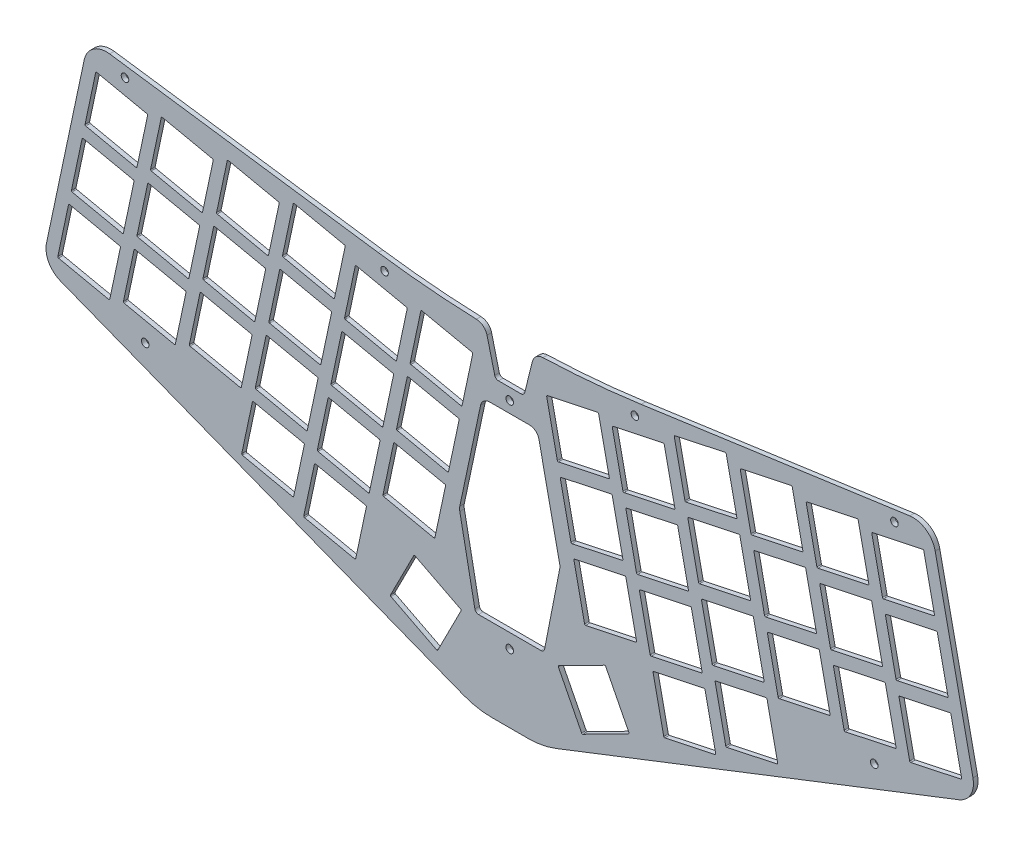
SolidWorks part; units mm, degrees
ref_plane "Front Plane" through (0, 0, 0) normal (0, 0, 1) x (1, 0, 0)
ref_plane "Top Plane" through (0, 0, 0) normal (0, 1, 0) x (1, 0, 0)
ref_plane "Right Plane" through (0, 0, 0) normal (1, 0, 0) x (0, 0, -1)
sketch "Model" plane through (0, 0, 0) normal (0, 0, 1) x (1, 0, 0)
  line L0 (118.9761, -36.3417) -> (119.3386, -36.3417)
  line L1 (109.9761, -36.3417) -> (109.6135, -36.3417)
  line L2 (130.2178, -33.5671) -> (126.6009, -34.9766)
  line L3 (98.7344, -33.5671) -> (102.3512, -34.9766)
  line L4 (114.4761, -36.3417) -> (109.9761, -36.3417)
  line L5 (114.4761, -36.3417) -> (118.9761, -36.3417)
  line L6 (118.4251, 42.1791) -> (120.4508, 50.3035)
  line L7 (110.527, 42.1791) -> (108.5014, 50.3035)
  line L8 (130.2178, -33.5671) -> (232.9153, 6.4558)
  line L9 (236.6055, 13.2938) -> (226.6558, 60.1035)
  line L10 (219.9519, 64.7976) -> (149.1302, 54.8443)
  line L11 (79.822, 54.8443) -> (9.0003, 64.7976)
  line L12 (2.2964, 60.1035) -> (-7.6533, 13.2938)
  line L13 (-3.9631, 6.4558) -> (98.7344, -33.5671)
  line L14 (111.4973, 41.421) -> (117.4548, 41.421)
  line L15 (119.9761, -34.3417) -> (108.9761, -34.3417)
  line L16 (120.4761, -22.3417) -> (120.4761, -33.8417)
  line L17 (108.9761, -21.8417) -> (119.9761, -21.8417)
  line L18 (108.4761, -33.8417) -> (108.4761, -22.3417)
  line L19 (123.6714, -13.7578) -> (127.6435, 6.5155)
  line L20 (105.2808, -13.7578) -> (101.3087, 6.5155)
  line L21 (106.2621, -14.5655) -> (122.69, -14.5655)
  line L22 (109.4761, 35.421) -> (109.2316, 35.421)
  line L23 (119.4761, 35.421) -> (119.7205, 35.421)
  line L24 (109.4761, 35.421) -> (119.4761, 35.421)
  line L25 (127.6339, 7.716) -> (122.1659, 33.4408)
  line L26 (101.3183, 7.716) -> (106.7863, 33.4408)
  line L27 (230.5128, 25.1235) -> (217.3078, 22.3167)
  line L28 (217.1153, 22.0202) -> (219.9221, 8.8152)
  line L29 (220.2186, 8.6226) -> (233.4236, 11.4294)
  line L30 (233.6161, 11.7259) -> (230.8093, 24.9309)
  line L31 (226.9263, 41.9965) -> (213.7213, 39.1897)
  line L32 (213.5288, 38.8932) -> (216.3356, 25.6882)
  line L33 (216.6321, 25.4957) -> (229.8371, 28.3025)
  line L34 (230.0297, 28.599) -> (227.2228, 41.804)
  line L35 (223.3399, 58.8696) -> (210.1349, 56.0628)
  line L36 (209.9423, 55.7663) -> (212.7491, 42.5613)
  line L37 (213.0456, 42.3687) -> (226.2506, 45.1755)
  line L38 (226.4432, 45.472) -> (223.6364, 58.677)
  line L39 (213.2239, 23.4933) -> (200.0189, 20.6865)
  line L40 (199.8264, 20.39) -> (202.6332, 7.185)
  line L41 (202.9297, 6.9924) -> (216.1347, 9.7992)
  line L42 (216.3273, 10.0958) -> (213.5205, 23.3007)
  line L43 (209.6375, 40.3663) -> (196.4325, 37.5595)
  line L44 (196.2399, 37.263) -> (199.0467, 24.058)
  line L45 (199.3432, 23.8655) -> (212.5482, 26.6723)
  line L46 (212.7408, 26.9688) -> (209.934, 40.1738)
  line L47 (206.051, 57.2394) -> (192.846, 54.4326)
  line L48 (192.6534, 54.1361) -> (195.4602, 40.9311)
  line L49 (195.7568, 40.7385) -> (208.9618, 43.5453)
  line L50 (209.1543, 43.8418) -> (206.3475, 57.0468)
  line L51 (195.8311, 22.3522) -> (182.6261, 19.5454)
  line L52 (182.4336, 19.2489) -> (185.2404, 6.0439)
  line L53 (185.5369, 5.8513) -> (198.7419, 8.6581)
  line L54 (198.9344, 8.9546) -> (196.1276, 22.1596)
  line L55 (192.2446, 39.2252) -> (179.0396, 36.4184)
  line L56 (178.8471, 36.1219) -> (181.6539, 22.9169)
  line L57 (181.9504, 22.7244) -> (195.1554, 25.5312)
  line L58 (195.348, 25.8277) -> (192.5412, 39.0327)
  line L59 (188.6582, 56.0983) -> (175.4532, 53.2915)
  line L60 (175.2606, 52.995) -> (178.0674, 39.79)
  line L61 (178.3639, 39.5974) -> (191.5689, 42.4042)
  line L62 (191.7615, 42.7007) -> (188.9547, 55.9057)
  line L63 (182.0248, 4.338) -> (168.8198, 1.5312)
  line L64 (168.6272, 1.2347) -> (171.434, -11.9703)
  line L65 (171.7305, -12.1628) -> (184.9355, -9.356)
  line L66 (185.1281, -9.0595) -> (182.3213, 4.1455)
  line L67 (178.4383, 21.2111) -> (165.2333, 18.4043)
  line L68 (165.0407, 18.1078) -> (167.8475, 4.9028)
  line L69 (168.1441, 4.7102) -> (181.3491, 7.517)
  line L70 (181.5416, 7.8135) -> (178.7348, 21.0185)
  line L71 (174.8518, 38.0841) -> (161.6468, 35.2773)
  line L72 (161.4543, 34.9808) -> (164.2611, 21.7758)
  line L73 (164.5576, 21.5833) -> (177.7626, 24.3901)
  line L74 (177.9551, 24.6866) -> (175.1483, 37.8916)
  line L75 (171.2653, 54.9572) -> (158.0603, 52.1504)
  line L76 (157.8678, 51.8539) -> (160.6746, 38.6489)
  line L77 (160.9711, 38.4563) -> (174.1761, 41.2631)
  line L78 (174.3687, 41.5596) -> (171.5619, 54.7646)
  line L79 (165.6715, -1.6938) -> (152.4665, -4.5006)
  line L80 (152.2739, -4.7971) -> (155.0808, -18.0021)
  line L81 (155.3773, -18.1947) -> (168.5823, -15.3879)
  line L82 (168.7748, -15.0914) -> (165.968, -1.8864)
  line L83 (162.085, 15.1792) -> (148.88, 12.3724)
  line L84 (148.6875, 12.0759) -> (151.4943, -1.1291)
  line L85 (151.7908, -1.3216) -> (164.9958, 1.4852)
  line L86 (165.1883, 1.7817) -> (162.3815, 14.9867)
  line L87 (158.4985, 32.0523) -> (145.2936, 29.2455)
  line L88 (145.101, 28.949) -> (147.9078, 15.744)
  line L89 (148.2043, 15.5514) -> (161.4093, 18.3582)
  line L90 (161.6019, 18.6547) -> (158.7951, 31.8597)
  line L91 (154.9121, 48.9253) -> (141.7071, 46.1185)
  line L92 (141.5145, 45.822) -> (144.3213, 32.617)
  line L93 (144.6178, 32.4245) -> (157.8228, 35.2313)
  line L94 (158.0154, 35.5278) -> (155.2086, 48.7328)
  line L95 (137.6232, 47.2952) -> (124.4182, 44.4883)
  line L96 (124.2256, 44.1918) -> (127.0325, 30.9868)
  line L97 (127.329, 30.7943) -> (140.534, 33.6011)
  line L98 (140.7265, 33.8976) -> (137.9197, 47.1026)
  line L99 (141.2097, 30.4221) -> (128.0047, 27.6153)
  line L100 (127.8121, 27.3188) -> (130.6189, 14.1138)
  line L101 (130.9154, 13.9212) -> (144.1204, 16.728)
  line L102 (144.313, 17.0246) -> (141.5062, 30.2295)
  line L103 (144.7962, 13.5491) -> (131.5912, 10.7423)
  line L104 (131.3986, 10.4457) -> (134.2054, -2.7593)
  line L105 (134.5019, -2.9518) -> (147.7069, -0.145)
  line L106 (147.8995, 0.1515) -> (145.0927, 13.3565)
  line L107 (139.4422, -9.5606) -> (127.4136, -15.6895)
  line L108 (127.3043, -16.0257) -> (133.4332, -28.0543)
  line L109 (133.7695, -28.1635) -> (145.7981, -22.0347)
  line L110 (145.9073, -21.6984) -> (139.7784, -9.6698)
  line L111 (101.5386, -15.6895) -> (89.51, -9.5606)
  line L112 (89.1737, -9.6698) -> (83.0449, -21.6984)
  line L113 (83.1541, -22.0347) -> (95.1827, -28.1635)
  line L114 (95.519, -28.0543) -> (101.6478, -16.0257)
  line L115 (97.361, 10.7423) -> (84.156, 13.5491)
  line L116 (83.8595, 13.3565) -> (81.0527, 0.1515)
  line L117 (81.2453, -0.145) -> (94.4502, -2.9518)
  line L118 (94.7468, -2.7593) -> (97.5536, 10.4457)
  line L119 (100.9475, 27.6153) -> (87.7425, 30.4221)
  line L120 (87.446, 30.2295) -> (84.6392, 17.0246)
  line L121 (84.8317, 16.728) -> (98.0367, 13.9212)
  line L122 (98.3332, 14.1138) -> (101.14, 27.3188)
  line L123 (104.534, 44.4883) -> (91.329, 47.2952)
  line L124 (91.0325, 47.1026) -> (88.2256, 33.8976)
  line L125 (88.4182, 33.6011) -> (101.6232, 30.7943)
  line L126 (101.9197, 30.9868) -> (104.7265, 44.1918)
  line L127 (76.4857, -4.5006) -> (63.2807, -1.6938)
  line L128 (62.9842, -1.8864) -> (60.1773, -15.0914)
  line L129 (60.3699, -15.3879) -> (73.5749, -18.1947)
  line L130 (73.8714, -18.0021) -> (76.6782, -4.7971)
  line L131 (80.0721, 12.3724) -> (66.8671, 15.1792)
  line L132 (66.5706, 14.9867) -> (63.7638, 1.7817)
  line L133 (63.9564, 1.4852) -> (77.1614, -1.3216)
  line L134 (77.4579, -1.1291) -> (80.2647, 12.0759)
  line L135 (83.6586, 29.2455) -> (70.4536, 32.0523)
  line L136 (70.1571, 31.8597) -> (67.3503, 18.6547)
  line L137 (67.5429, 18.3582) -> (80.7479, 15.5514)
  line L138 (81.0444, 15.744) -> (83.8512, 28.949)
  line L139 (87.2451, 46.1185) -> (74.0401, 48.9253)
  line L140 (73.7436, 48.7328) -> (70.9368, 35.5278)
  line L141 (71.1293, 35.2313) -> (84.3343, 32.4245)
  line L142 (84.6308, 32.617) -> (87.4377, 45.822)
  line L143 (60.1324, 1.5312) -> (46.9274, 4.338)
  line L144 (46.6309, 4.1455) -> (43.8241, -9.0595)
  line L145 (44.0166, -9.356) -> (57.2216, -12.1628)
  line L146 (57.5181, -11.9703) -> (60.325, 1.2347)
  line L147 (63.7189, 18.4043) -> (50.5139, 21.2111)
  line L148 (50.2174, 21.0185) -> (47.4106, 7.8135)
  line L149 (47.6031, 7.517) -> (60.8081, 4.7102)
  line L150 (61.1046, 4.9028) -> (63.9114, 18.1078)
  line L151 (67.3054, 35.2773) -> (54.1004, 38.0841)
  line L152 (53.8038, 37.8916) -> (50.997, 24.6866)
  line L153 (51.1896, 24.3901) -> (64.3946, 21.5833)
  line L154 (64.6911, 21.7758) -> (67.4979, 34.9808)
  line L155 (70.8918, 52.1504) -> (57.6868, 54.9572)
  line L156 (57.3903, 54.7646) -> (54.5835, 41.5596)
  line L157 (54.7761, 41.2631) -> (67.9811, 38.4563)
  line L158 (68.2776, 38.6489) -> (71.0844, 51.8539)
  line L159 (46.5186, 19.2489) -> (45.1152, 12.6464)
  line L160 (33.1211, 22.3522) -> (46.326, 19.5454)
  line L161 (30.0177, 8.9546) -> (32.8245, 22.1596)
  line L162 (43.4153, 5.8513) -> (30.2103, 8.6581)
  line L163 (45.1152, 12.6464) -> (43.7118, 6.0439)
  line L164 (50.1051, 36.1219) -> (48.7017, 29.5194)
  line L165 (36.7075, 39.2252) -> (49.9125, 36.4184)
  line L166 (33.6042, 25.8277) -> (36.411, 39.0327)
  line L167 (47.0018, 22.7244) -> (33.7968, 25.5312)
  line L168 (48.7017, 29.5194) -> (47.2983, 22.9169)
  line L169 (53.6916, 52.995) -> (52.2882, 46.3925)
  line L170 (40.294, 56.0983) -> (53.499, 53.2915)
  line L171 (37.1907, 42.7007) -> (39.9975, 55.9057)
  line L172 (50.5882, 39.5974) -> (37.3832, 42.4042)
  line L173 (52.2882, 46.3925) -> (50.8848, 39.79)
  line L174 (29.1258, 20.39) -> (27.7224, 13.7875)
  line L175 (15.7282, 23.4933) -> (28.9332, 20.6865)
  line L176 (12.6249, 10.0958) -> (15.4317, 23.3007)
  line L177 (26.0225, 6.9924) -> (12.8175, 9.7992)
  line L178 (27.7224, 13.7875) -> (26.319, 7.185)
  line L179 (32.7123, 37.263) -> (31.3089, 30.6605)
  line L180 (19.3147, 40.3663) -> (32.5197, 37.5595)
  line L181 (16.2114, 26.9688) -> (19.0182, 40.1738)
  line L182 (29.6089, 23.8655) -> (16.4039, 26.6723)
  line L183 (31.3089, 30.6605) -> (29.9055, 24.058)
  line L184 (19.7979, 43.8418) -> (21.2013, 50.4443)
  line L185 (33.1954, 40.7385) -> (19.9904, 43.5453)
  line L186 (36.2987, 54.1361) -> (33.4919, 40.9311)
  line L187 (22.9012, 57.2394) -> (36.1062, 54.4326)
  line L188 (21.2013, 50.4443) -> (22.6047, 57.0468)
  line L189 (-4.664, 11.7259) -> (-3.2606, 18.3284)
  line L190 (8.7336, 8.6226) -> (-4.4714, 11.4294)
  line L191 (11.8369, 22.0202) -> (9.0301, 8.8152)
  line L192 (-1.5606, 25.1235) -> (11.6444, 22.3167)
  line L193 (-3.2606, 18.3284) -> (-1.8572, 24.9309)
  line L194 (15.2308, 39.1897) -> (8.6283, 40.5931)
  line L195 (12.6166, 25.6882) -> (15.4234, 38.8932)
  line L196 (-0.8849, 28.3025) -> (12.3201, 25.4957)
  line L197 (1.7293, 41.804) -> (-1.0775, 28.599)
  line L198 (8.6283, 40.5931) -> (2.0258, 41.9965)
  line L199 (2.509, 45.472) -> (3.9124, 52.0745)
  line L200 (15.9065, 42.3687) -> (2.7016, 45.1755)
  line L201 (19.0099, 55.7663) -> (16.2031, 42.5613)
  line L202 (5.6123, 58.8696) -> (18.8173, 56.0628)
  line L203 (3.9124, 52.0745) -> (5.3158, 58.677)
  line L206 (114.4761, -19.3417) -> (114.4761, -17.3417) construction
  line L207 (115.4761, -18.3417) -> (113.4761, -18.3417) construction
  circle A0 centre (215.9057, 61.3788) radius 1
  circle A1 centre (13.0465, 61.3788) radius 1
  circle A2 centre (148.1114, -4.3098) radius 1
  circle A3 centre (80.8407, -4.3098) radius 1
  circle A4 centre (210.5718, 3.5051) radius 1
  circle A5 centre (147.4779, 51.4345) radius 1
  circle A6 centre (81.4742, 51.4345) radius 1
  circle A7 centre (18.3804, 3.5051) radius 1
  circle A8 centre (114.4761, -18.3417) radius 1
  circle A9 centre (114.4761, 38.421) radius 1
  arc A10 (108.4761, -33.8417) -> (108.9761, -34.3417) centre (108.9761, -33.8417) ccw
  arc A11 (119.9761, -34.3417) -> (120.4761, -33.8417) centre (119.9761, -33.8417) ccw
  arc A12 (120.4761, -22.3417) -> (119.9761, -21.8417) centre (119.9761, -22.3417) ccw
  arc A13 (108.9761, -21.8417) -> (108.4761, -22.3417) centre (108.9761, -22.3417) ccw
  arc A14 (122.69, -14.5655) -> (123.6714, -13.7578) centre (122.69, -13.5655) ccw
  arc A15 (105.2808, -13.7578) -> (106.2621, -14.5655) centre (106.2621, -13.5655) ccw
  arc A16 (127.6435, 6.5155) -> (127.6339, 7.716) centre (124.6994, 7.0923) ccw
  arc A17 (101.3183, 7.716) -> (101.3087, 6.5155) centre (104.2527, 7.0923) ccw
  arc A18 (122.1659, 33.4408) -> (119.7205, 35.421) centre (119.7205, 32.921) ccw
  arc A19 (109.2316, 35.421) -> (106.7863, 33.4408) centre (109.2316, 32.921) ccw
  arc A20 (46.5186, 19.2489) -> (46.326, 19.5454) centre (46.2741, 19.3008) ccw
  arc A21 (30.0177, 8.9546) -> (30.2103, 8.6581) centre (30.2623, 8.9027) ccw
  arc A22 (33.1211, 22.3522) -> (32.8245, 22.1596) centre (33.0691, 22.1077) ccw
  arc A23 (43.4153, 5.8513) -> (43.7118, 6.0439) centre (43.4673, 6.0959) ccw
  arc A24 (50.1051, 36.1219) -> (49.9125, 36.4184) centre (49.8605, 36.1739) ccw
  arc A25 (36.7075, 39.2252) -> (36.411, 39.0327) centre (36.6556, 38.9807) ccw
  arc A26 (33.6042, 25.8277) -> (33.7968, 25.5312) centre (33.8487, 25.7757) ccw
  arc A27 (47.0018, 22.7244) -> (47.2983, 22.9169) centre (47.0537, 22.9689) ccw
  arc A28 (53.6916, 52.995) -> (53.499, 53.2915) centre (53.447, 53.0469) ccw
  arc A29 (40.294, 56.0983) -> (39.9975, 55.9057) centre (40.242, 55.8537) ccw
  arc A30 (37.1907, 42.7007) -> (37.3832, 42.4042) centre (37.4352, 42.6488) ccw
  arc A31 (50.5882, 39.5974) -> (50.8848, 39.79) centre (50.6402, 39.8419) ccw
  arc A32 (29.1258, 20.39) -> (28.9332, 20.6865) centre (28.8812, 20.442) ccw
  arc A33 (15.7282, 23.4933) -> (15.4317, 23.3007) centre (15.6763, 23.2488) ccw
  arc A34 (12.6249, 10.0958) -> (12.8175, 9.7992) centre (12.8694, 10.0438) ccw
  arc A35 (26.0225, 6.9924) -> (26.319, 7.185) centre (26.0744, 7.237) ccw
  arc A36 (19.3147, 40.3663) -> (19.0182, 40.1738) centre (19.2627, 40.1218) ccw
  arc A37 (32.7123, 37.263) -> (32.5197, 37.5595) centre (32.4677, 37.315) ccw
  arc A38 (16.2114, 26.9688) -> (16.4039, 26.6723) centre (16.4559, 26.9168) ccw
  arc A39 (29.6089, 23.8655) -> (29.9055, 24.058) centre (29.6609, 24.11) ccw
  arc A40 (19.7979, 43.8418) -> (19.9904, 43.5453) centre (20.0424, 43.7899) ccw
  arc A41 (36.2987, 54.1361) -> (36.1062, 54.4326) centre (36.0542, 54.188) ccw
  arc A42 (33.1954, 40.7385) -> (33.4919, 40.9311) centre (33.2474, 40.9831) ccw
  arc A43 (22.9012, 57.2394) -> (22.6047, 57.0468) centre (22.8492, 56.9949) ccw
  arc A44 (-4.664, 11.7259) -> (-4.4714, 11.4294) centre (-4.4194, 11.674) ccw
  arc A45 (11.8369, 22.0202) -> (11.6444, 22.3167) centre (11.5924, 22.0721) ccw
  arc A46 (8.7336, 8.6226) -> (9.0301, 8.8152) centre (8.7856, 8.8671) ccw
  arc A47 (-1.5606, 25.1235) -> (-1.8572, 24.9309) centre (-1.6126, 24.8789) ccw
  arc A48 (15.4234, 38.8932) -> (15.2308, 39.1897) centre (15.1789, 38.9452) ccw
  arc A49 (12.3201, 25.4957) -> (12.6166, 25.6882) centre (12.372, 25.7402) ccw
  arc A50 (-1.0775, 28.599) -> (-0.8849, 28.3025) centre (-0.8329, 28.547) ccw
  arc A51 (2.0258, 41.9965) -> (1.7293, 41.804) centre (1.9739, 41.752) ccw
  arc A52 (2.509, 45.472) -> (2.7016, 45.1755) centre (2.7535, 45.42) ccw
  arc A53 (19.0099, 55.7663) -> (18.8173, 56.0628) centre (18.7653, 55.8182) ccw
  arc A54 (15.9065, 42.3687) -> (16.2031, 42.5613) centre (15.9585, 42.6132) ccw
  arc A55 (5.6123, 58.8696) -> (5.3158, 58.677) centre (5.5603, 58.625) ccw
  arc A56 (102.3512, -34.9766) -> (109.6135, -36.3417) centre (109.6135, -16.3417) ccw
  arc A57 (119.3386, -36.3417) -> (126.6009, -34.9766) centre (119.3386, -16.3417) ccw
  arc A58 (108.5014, 50.3035) -> (105.6963, 52.5758) centre (105.5905, 49.5777) ccw
  arc A59 (123.2559, 52.5758) -> (120.4508, 50.3035) centre (123.3617, 49.5777) ccw
  arc A60 (117.4548, 41.421) -> (118.4251, 42.1791) centre (117.4548, 42.421) ccw
  arc A61 (110.527, 42.1791) -> (111.4973, 41.421) centre (111.4973, 42.421) ccw
  arc A62 (232.9153, 6.4558) -> (236.6055, 13.2938) centre (230.7366, 12.0463) ccw
  arc A63 (226.6558, 60.1035) -> (219.9519, 64.7976) centre (220.7869, 58.856) ccw
  arc A64 (123.2559, 52.5758) -> (149.1302, 54.8443) centre (114.4761, 301.421) ccw
  arc A65 (79.822, 54.8443) -> (105.6963, 52.5758) centre (114.4761, 301.421) ccw
  arc A66 (9.0003, 64.7976) -> (2.2964, 60.1035) centre (8.1653, 58.856) ccw
  arc A67 (-7.6533, 13.2938) -> (-3.9631, 6.4558) centre (-1.7844, 12.0463) ccw
  arc A68 (217.3078, 22.3167) -> (217.1153, 22.0202) centre (217.3598, 22.0721) ccw
  arc A69 (219.9221, 8.8152) -> (220.2186, 8.6226) centre (220.1666, 8.8671) ccw
  arc A70 (233.4236, 11.4294) -> (233.6161, 11.7259) centre (233.3716, 11.674) ccw
  arc A71 (230.8093, 24.9309) -> (230.5128, 25.1235) centre (230.5648, 24.8789) ccw
  arc A72 (213.7213, 39.1897) -> (213.5288, 38.8932) centre (213.7733, 38.9452) ccw
  arc A73 (216.3356, 25.6882) -> (216.6321, 25.4957) centre (216.5801, 25.7402) ccw
  arc A74 (229.8371, 28.3025) -> (230.0297, 28.599) centre (229.7851, 28.547) ccw
  arc A75 (227.2228, 41.804) -> (226.9263, 41.9965) centre (226.9783, 41.752) ccw
  arc A76 (210.1349, 56.0628) -> (209.9423, 55.7663) centre (210.1868, 55.8182) ccw
  arc A77 (212.7491, 42.5613) -> (213.0456, 42.3687) centre (212.9937, 42.6132) ccw
  arc A78 (226.2506, 45.1755) -> (226.4432, 45.472) centre (226.1986, 45.42) ccw
  arc A79 (223.6364, 58.677) -> (223.3399, 58.8696) centre (223.3918, 58.625) ccw
  arc A80 (200.0189, 20.6865) -> (199.8264, 20.39) centre (200.0709, 20.442) ccw
  arc A81 (202.6332, 7.185) -> (202.9297, 6.9924) centre (202.8777, 7.237) ccw
  arc A82 (216.1347, 9.7992) -> (216.3273, 10.0958) centre (216.0827, 10.0438) ccw
  arc A83 (213.5205, 23.3007) -> (213.2239, 23.4933) centre (213.2759, 23.2488) ccw
  arc A84 (196.4325, 37.5595) -> (196.2399, 37.263) centre (196.4845, 37.315) ccw
  arc A85 (199.0467, 24.058) -> (199.3432, 23.8655) centre (199.2913, 24.11) ccw
  arc A86 (212.5482, 26.6723) -> (212.7408, 26.9688) centre (212.4963, 26.9168) ccw
  arc A87 (209.934, 40.1738) -> (209.6375, 40.3663) centre (209.6894, 40.1218) ccw
  arc A88 (192.846, 54.4326) -> (192.6534, 54.1361) centre (192.898, 54.188) ccw
  arc A89 (195.4602, 40.9311) -> (195.7568, 40.7385) centre (195.7048, 40.9831) ccw
  arc A90 (208.9618, 43.5453) -> (209.1543, 43.8418) centre (208.9098, 43.7899) ccw
  arc A91 (206.3475, 57.0468) -> (206.051, 57.2394) centre (206.103, 56.9949) ccw
  arc A92 (182.6261, 19.5454) -> (182.4336, 19.2489) centre (182.6781, 19.3008) ccw
  arc A93 (185.2404, 6.0439) -> (185.5369, 5.8513) centre (185.4849, 6.0959) ccw
  arc A94 (198.7419, 8.6581) -> (198.9344, 8.9546) centre (198.6899, 8.9027) ccw
  arc A95 (196.1276, 22.1596) -> (195.8311, 22.3522) centre (195.8831, 22.1077) ccw
  arc A96 (179.0396, 36.4184) -> (178.8471, 36.1219) centre (179.0916, 36.1739) ccw
  arc A97 (181.6539, 22.9169) -> (181.9504, 22.7244) centre (181.8984, 22.9689) ccw
  arc A98 (195.1554, 25.5312) -> (195.348, 25.8277) centre (195.1034, 25.7757) ccw
  arc A99 (192.5412, 39.0327) -> (192.2446, 39.2252) centre (192.2966, 38.9807) ccw
  arc A100 (175.4532, 53.2915) -> (175.2606, 52.995) centre (175.5051, 53.0469) ccw
  arc A101 (178.0674, 39.79) -> (178.3639, 39.5974) centre (178.312, 39.8419) ccw
  arc A102 (191.5689, 42.4042) -> (191.7615, 42.7007) centre (191.5169, 42.6488) ccw
  arc A103 (188.9547, 55.9057) -> (188.6582, 56.0983) centre (188.7101, 55.8537) ccw
  arc A104 (168.8198, 1.5312) -> (168.6272, 1.2347) centre (168.8718, 1.2867) ccw
  arc A105 (171.434, -11.9703) -> (171.7305, -12.1628) centre (171.6786, -11.9183) ccw
  arc A106 (184.9355, -9.356) -> (185.1281, -9.0595) centre (184.8836, -9.1115) ccw
  arc A107 (182.3213, 4.1455) -> (182.0248, 4.338) centre (182.0767, 4.0935) ccw
  arc A108 (165.2333, 18.4043) -> (165.0407, 18.1078) centre (165.2853, 18.1597) ccw
  arc A109 (167.8475, 4.9028) -> (168.1441, 4.7102) centre (168.0921, 4.9547) ccw
  arc A110 (181.3491, 7.517) -> (181.5416, 7.8135) centre (181.2971, 7.7616) ccw
  arc A111 (178.7348, 21.0185) -> (178.4383, 21.2111) centre (178.4903, 20.9665) ccw
  arc A112 (161.6468, 35.2773) -> (161.4543, 34.9808) centre (161.6988, 35.0328) ccw
  arc A113 (164.2611, 21.7758) -> (164.5576, 21.5833) centre (164.5056, 21.8278) ccw
  arc A114 (177.7626, 24.3901) -> (177.9551, 24.6866) centre (177.7106, 24.6346) ccw
  arc A115 (175.1483, 37.8916) -> (174.8518, 38.0841) centre (174.9038, 37.8396) ccw
  arc A116 (158.0603, 52.1504) -> (157.8678, 51.8539) centre (158.1123, 51.9058) ccw
  arc A117 (160.6746, 38.6489) -> (160.9711, 38.4563) centre (160.9191, 38.7008) ccw
  arc A118 (174.1761, 41.2631) -> (174.3687, 41.5596) centre (174.1241, 41.5076) ccw
  arc A119 (171.5619, 54.7646) -> (171.2653, 54.9572) centre (171.3173, 54.7126) ccw
  arc A120 (152.4665, -4.5006) -> (152.2739, -4.7971) centre (152.5185, -4.7452) ccw
  arc A121 (155.0808, -18.0021) -> (155.3773, -18.1947) centre (155.3253, -17.9501) ccw
  arc A122 (168.5823, -15.3879) -> (168.7748, -15.0914) centre (168.5303, -15.1433) ccw
  arc A123 (165.968, -1.8864) -> (165.6715, -1.6938) centre (165.7235, -1.9383) ccw
  arc A124 (148.88, 12.3724) -> (148.6875, 12.0759) centre (148.932, 12.1279) ccw
  arc A125 (151.4943, -1.1291) -> (151.7908, -1.3216) centre (151.7388, -1.0771) ccw
  arc A126 (164.9958, 1.4852) -> (165.1883, 1.7817) centre (164.9438, 1.7297) ccw
  arc A127 (162.3815, 14.9867) -> (162.085, 15.1792) centre (162.137, 14.9347) ccw
  arc A128 (145.2936, 29.2455) -> (145.101, 28.949) centre (145.3455, 29.0009) ccw
  arc A129 (147.9078, 15.744) -> (148.2043, 15.5514) centre (148.1523, 15.7959) ccw
  arc A130 (161.4093, 18.3582) -> (161.6019, 18.6547) centre (161.3573, 18.6028) ccw
  arc A131 (158.7951, 31.8597) -> (158.4985, 32.0523) centre (158.5505, 31.8078) ccw
  arc A132 (141.7071, 46.1185) -> (141.5145, 45.822) centre (141.7591, 45.874) ccw
  arc A133 (144.3213, 32.617) -> (144.6178, 32.4245) centre (144.5659, 32.669) ccw
  arc A134 (157.8228, 35.2313) -> (158.0154, 35.5278) centre (157.7709, 35.4758) ccw
  arc A135 (155.2086, 48.7328) -> (154.9121, 48.9253) centre (154.964, 48.6808) ccw
  arc A136 (124.4182, 44.4883) -> (124.2256, 44.1918) centre (124.4702, 44.2438) ccw
  arc A137 (127.0325, 30.9868) -> (127.329, 30.7943) centre (127.277, 31.0388) ccw
  arc A138 (140.534, 33.6011) -> (140.7265, 33.8976) centre (140.482, 33.8456) ccw
  arc A139 (137.9197, 47.1026) -> (137.6232, 47.2952) centre (137.6752, 47.0506) ccw
  arc A140 (128.0047, 27.6153) -> (127.8121, 27.3188) centre (128.0567, 27.3708) ccw
  arc A141 (130.6189, 14.1138) -> (130.9154, 13.9212) centre (130.8635, 14.1658) ccw
  arc A142 (144.1204, 16.728) -> (144.313, 17.0246) centre (144.0685, 16.9726) ccw
  arc A143 (141.5062, 30.2295) -> (141.2097, 30.4221) centre (141.2617, 30.1776) ccw
  arc A144 (131.5912, 10.7423) -> (131.3986, 10.4457) centre (131.6431, 10.4977) ccw
  arc A145 (134.2054, -2.7593) -> (134.5019, -2.9518) centre (134.4499, -2.7073) ccw
  arc A146 (147.7069, -0.145) -> (147.8995, 0.1515) centre (147.6549, 0.0995) ccw
  arc A147 (145.0927, 13.3565) -> (144.7962, 13.5491) centre (144.8481, 13.3045) ccw
  arc A148 (127.4136, -15.6895) -> (127.3043, -16.0257) centre (127.5271, -15.9122) ccw
  arc A149 (133.4332, -28.0543) -> (133.7695, -28.1635) centre (133.656, -27.9408) ccw
  arc A150 (145.7981, -22.0347) -> (145.9073, -21.6984) centre (145.6846, -21.8119) ccw
  arc A151 (139.7784, -9.6698) -> (139.4422, -9.5606) centre (139.5557, -9.7833) ccw
  arc A152 (89.51, -9.5606) -> (89.1737, -9.6698) centre (89.3965, -9.7833) ccw
  arc A153 (83.0449, -21.6984) -> (83.1541, -22.0347) centre (83.2676, -21.8119) ccw
  arc A154 (95.1827, -28.1635) -> (95.519, -28.0543) centre (95.2962, -27.9408) ccw
  arc A155 (101.6478, -16.0257) -> (101.5386, -15.6895) centre (101.4251, -15.9122) ccw
  arc A156 (84.156, 13.5491) -> (83.8595, 13.3565) centre (84.104, 13.3045) ccw
  arc A157 (81.0527, 0.1515) -> (81.2453, -0.145) centre (81.2972, 0.0995) ccw
  arc A158 (94.4502, -2.9518) -> (94.7468, -2.7593) centre (94.5022, -2.7073) ccw
  arc A159 (97.5536, 10.4457) -> (97.361, 10.7423) centre (97.309, 10.4977) ccw
  arc A160 (87.7425, 30.4221) -> (87.446, 30.2295) centre (87.6905, 30.1776) ccw
  arc A161 (84.6392, 17.0246) -> (84.8317, 16.728) centre (84.8837, 16.9726) ccw
  arc A162 (98.0367, 13.9212) -> (98.3332, 14.1138) centre (98.0887, 14.1658) ccw
  arc A163 (101.14, 27.3188) -> (100.9475, 27.6153) centre (100.8955, 27.3708) ccw
  arc A164 (91.329, 47.2952) -> (91.0325, 47.1026) centre (91.277, 47.0506) ccw
  arc A165 (88.2256, 33.8976) -> (88.4182, 33.6011) centre (88.4702, 33.8456) ccw
  arc A166 (101.6232, 30.7943) -> (101.9197, 30.9868) centre (101.6752, 31.0388) ccw
  arc A167 (104.7265, 44.1918) -> (104.534, 44.4883) centre (104.482, 44.2438) ccw
  arc A168 (63.2807, -1.6938) -> (62.9842, -1.8864) centre (63.2287, -1.9383) ccw
  arc A169 (60.1773, -15.0914) -> (60.3699, -15.3879) centre (60.4219, -15.1433) ccw
  arc A170 (73.5749, -18.1947) -> (73.8714, -18.0021) centre (73.6269, -17.9501) ccw
  arc A171 (76.6782, -4.7971) -> (76.4857, -4.5006) centre (76.4337, -4.7452) ccw
  arc A172 (66.8671, 15.1792) -> (66.5706, 14.9867) centre (66.8152, 14.9347) ccw
  arc A173 (63.7638, 1.7817) -> (63.9564, 1.4852) centre (64.0084, 1.7297) ccw
  arc A174 (77.1614, -1.3216) -> (77.4579, -1.1291) centre (77.2134, -1.0771) ccw
  arc A175 (80.2647, 12.0759) -> (80.0721, 12.3724) centre (80.0202, 12.1279) ccw
  arc A176 (70.4536, 32.0523) -> (70.1571, 31.8597) centre (70.4016, 31.8078) ccw
  arc A177 (67.3503, 18.6547) -> (67.5429, 18.3582) centre (67.5948, 18.6028) ccw
  arc A178 (80.7479, 15.5514) -> (81.0444, 15.744) centre (80.7998, 15.7959) ccw
  arc A179 (83.8512, 28.949) -> (83.6586, 29.2455) centre (83.6066, 29.0009) ccw
  arc A180 (74.0401, 48.9253) -> (73.7436, 48.7328) centre (73.9881, 48.6808) ccw
  arc A181 (70.9368, 35.5278) -> (71.1293, 35.2313) centre (71.1813, 35.4758) ccw
  arc A182 (84.3343, 32.4245) -> (84.6308, 32.617) centre (84.3863, 32.669) ccw
  arc A183 (87.4377, 45.822) -> (87.2451, 46.1185) centre (87.1931, 45.874) ccw
  arc A184 (46.9274, 4.338) -> (46.6309, 4.1455) centre (46.8754, 4.0935) ccw
  arc A185 (43.8241, -9.0595) -> (44.0166, -9.356) centre (44.0686, -9.1115) ccw
  arc A186 (57.2216, -12.1628) -> (57.5181, -11.9703) centre (57.2736, -11.9183) ccw
  arc A187 (60.325, 1.2347) -> (60.1324, 1.5312) centre (60.0804, 1.2867) ccw
  arc A188 (50.5139, 21.2111) -> (50.2174, 21.0185) centre (50.4619, 20.9665) ccw
  arc A189 (47.4106, 7.8135) -> (47.6031, 7.517) centre (47.6551, 7.7616) ccw
  arc A190 (60.8081, 4.7102) -> (61.1046, 4.9028) centre (60.8601, 4.9547) ccw
  arc A191 (63.9114, 18.1078) -> (63.7189, 18.4043) centre (63.6669, 18.1597) ccw
  arc A192 (54.1004, 38.0841) -> (53.8038, 37.8916) centre (54.0484, 37.8396) ccw
  arc A193 (50.997, 24.6866) -> (51.1896, 24.3901) centre (51.2416, 24.6346) ccw
  arc A194 (64.3946, 21.5833) -> (64.6911, 21.7758) centre (64.4466, 21.8278) ccw
  arc A195 (67.4979, 34.9808) -> (67.3054, 35.2773) centre (67.2534, 35.0328) ccw
  arc A196 (57.6868, 54.9572) -> (57.3903, 54.7646) centre (57.6349, 54.7126) ccw
  arc A197 (54.5835, 41.5596) -> (54.7761, 41.2631) centre (54.828, 41.5076) ccw
  arc A198 (67.9811, 38.4563) -> (68.2776, 38.6489) centre (68.033, 38.7008) ccw
  arc A199 (71.0844, 51.8539) -> (70.8918, 52.1504) centre (70.8399, 51.9058) ccw
extrude "Boss-Extrude1" add sketch "Model" along normal blind 1.2 contours A3 | L12 A67 L13 L3 A56 L1 L4 L5 L0 A57 L2 L8 A62 L9 A63 L10 A64 A59 L6 A60 L14 A61 L7 A58 A65 L11 A66 A199 L158 A198 L157 A197 L156 A196 L155 A195 L154 A194 L153 A193 L152 A192 L151 A191 L150 A190 L149 A189 | A2 | L17 A13 L18 A10 L15 A11 L16 A12 region at (116.7261, -36.0771, 0) region at (114.4761, -28.0917, 0) region at (148.1114, -4.3098, 0) region at (80.8407, -4.3098, 0)
